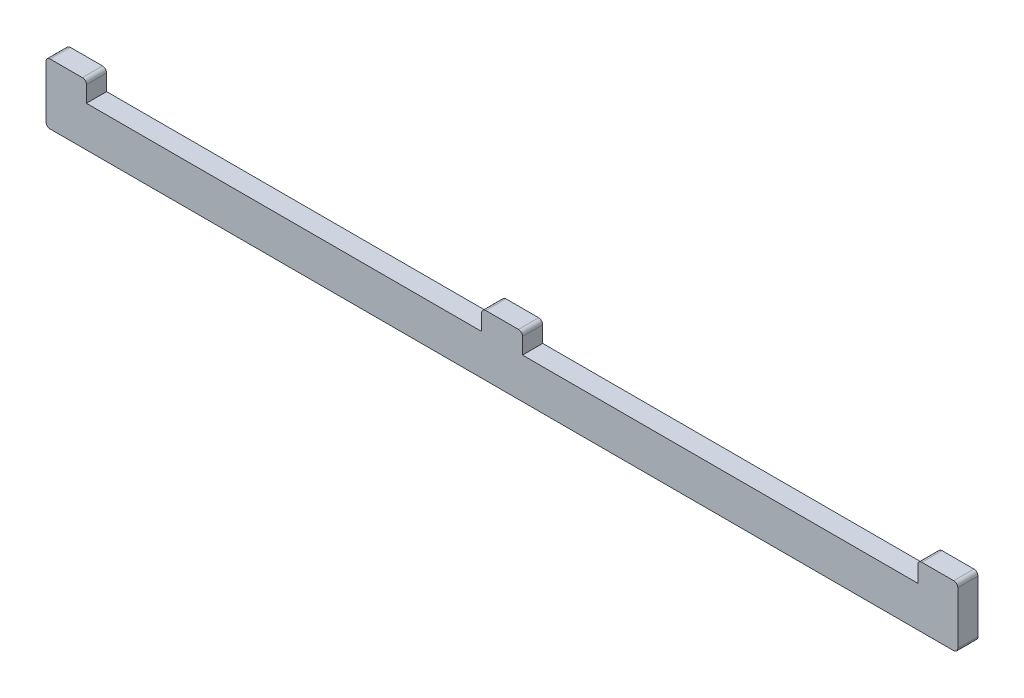
SolidWorks part; units mm, degrees
ref_plane "Front" through (0, 0, 0) normal (0, 0, 1) x (1, 0, 0)
ref_plane "Top" through (0, 0, 0) normal (0, 1, 0) x (1, 0, 0)
ref_plane "Right" through (0, 0, 0) normal (1, 0, 0) x (0, 0, -1)
sketch "Sketch1" plane through (0, 0, 0) normal (0, 0, 1) x (1, 0, 0)
  line L0 (117.9, 10) -> (215.7, 10)
  line L1 (1, 0) -> (224.6, 0)
  line L3 (10, 10) -> (107.8, 10)
  line L6 (107.8, 10) -> (107.8, 14)
  line L7 (108.8, 15) -> (116.9, 15)
  line L8 (117.9, 10) -> (117.9, 14)
  line L9 (225.6, 14) -> (225.6, 1)
  line L12 (1, 15) -> (9, 15)
  line L13 (10, 10) -> (10, 14)
  line L16 (224.6, 15) -> (216.7, 15)
  line L17 (215.7, 10) -> (215.7, 14)
  line L18 (0, 14) -> (0, 1)
  arc A0 (225.6, 1) -> (224.6, 0) centre (224.6, 1) cw
  arc A1 (1, 0) -> (0, 1) centre (1, 1) cw
  arc A2 (117.9, 14) -> (116.9, 15) centre (116.9, 14) ccw
  arc A3 (108.8, 15) -> (107.8, 14) centre (108.8, 14) ccw
  arc A4 (10, 14) -> (9, 15) centre (9, 14) ccw
  arc A5 (1, 15) -> (0, 14) centre (1, 14) ccw
  arc A6 (225.6, 14) -> (224.6, 15) centre (224.6, 14) ccw
  arc A7 (216.7, 15) -> (215.7, 14) centre (216.7, 14) ccw
  point P11 (225.6, 0)
  point P14 (0, 0)
  point P17 (117.9, 15)
  point P20 (107.8, 15)
  point P29 (10, 15)
  point P32 (-0.1, 15)
  point P35 (225.8, 15)
  point P38 (215.7, 15)
  dimension "D6" = 1
  dimension "D11" = 1
  dimension "D2" = 97.8
  dimension "D3" = 97.8
  dimension "D4" = 10.1
  dimension "D5" = 5
  dimension "D7" = 10.1
  dimension "D8" = 5
  dimension "D9" = 5
  dimension "D10" = 10.1
  dimension "D12" = 10
extrude "Boss-Extrude1" add sketch "Sketch1" along normal blind 5
